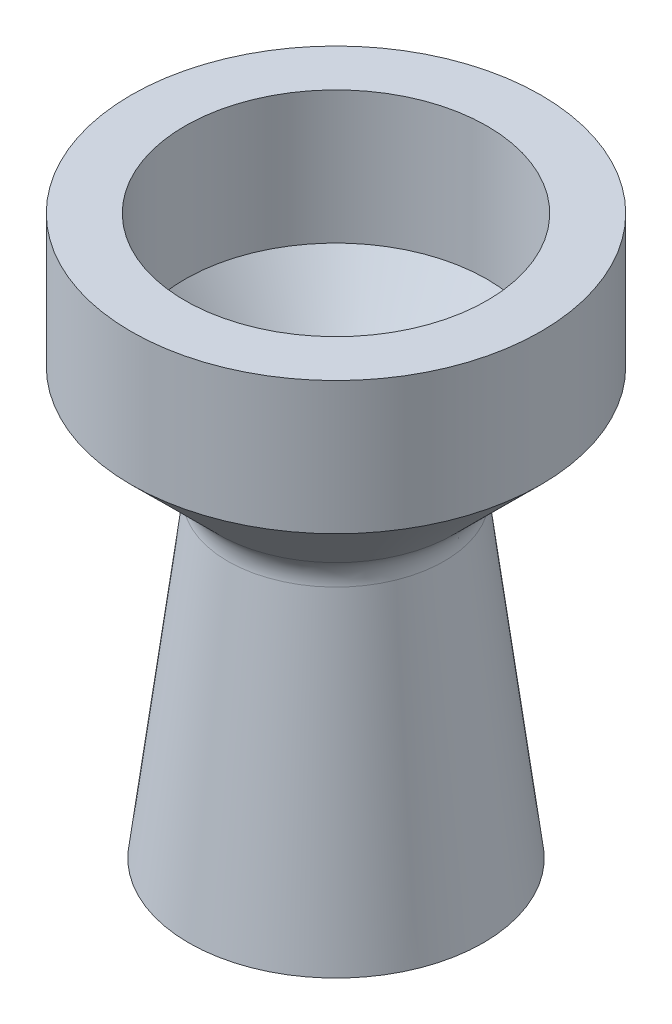
SolidWorks part; units mm, degrees
material "7075-T6 (SN)"
ref_plane "Front Plane" through (0, 0, 0) normal (0, 0, 1) x (1, 0, 0)
ref_plane "Top Plane" through (0, 0, 0) normal (0, 1, 0) x (1, 0, 0)
ref_plane "Right Plane" through (0, 0, 0) normal (1, 0, 0) x (0, 0, -1)
sketch "Sketch1" plane through (0, 0, 0) normal (0, 0, 1) x (1, 0, 0)
  line L0 (-30.5, -4.75) -> (-30.5, -24.5)
  line L1 (-30.5, -24.5) -> (-17.5465, -37.3887)
  line L2 (0, 0) -> (0, 10) construction
  line L3 (-30.5, -4.75) -> (-22.5, -4.75)
  line L5 (-22.5, -4.75) -> (-22.5, -24.5)
  line L6 (-22.5, -24.5) -> (-12, -39.1202)
  line L7 (-12, -39.1202) -> (-18.4243, -87.8553)
  line L8 (-16.1121, -41.5559) -> (-21.9243, -87.8553)
  line L9 (-21.9243, -87.8553) -> (-18.4243, -87.8553)
  arc A0 (-16.1121, -41.5559) -> (-17.5465, -37.3887) centre (-21.0731, -40.9331) ccw
  point P11 (0, 0)
  dimension "D1" = 3.5
  dimension "D2" = 5
revolve "Revolve1" add sketch "Sketch1" angle 360 about L2
